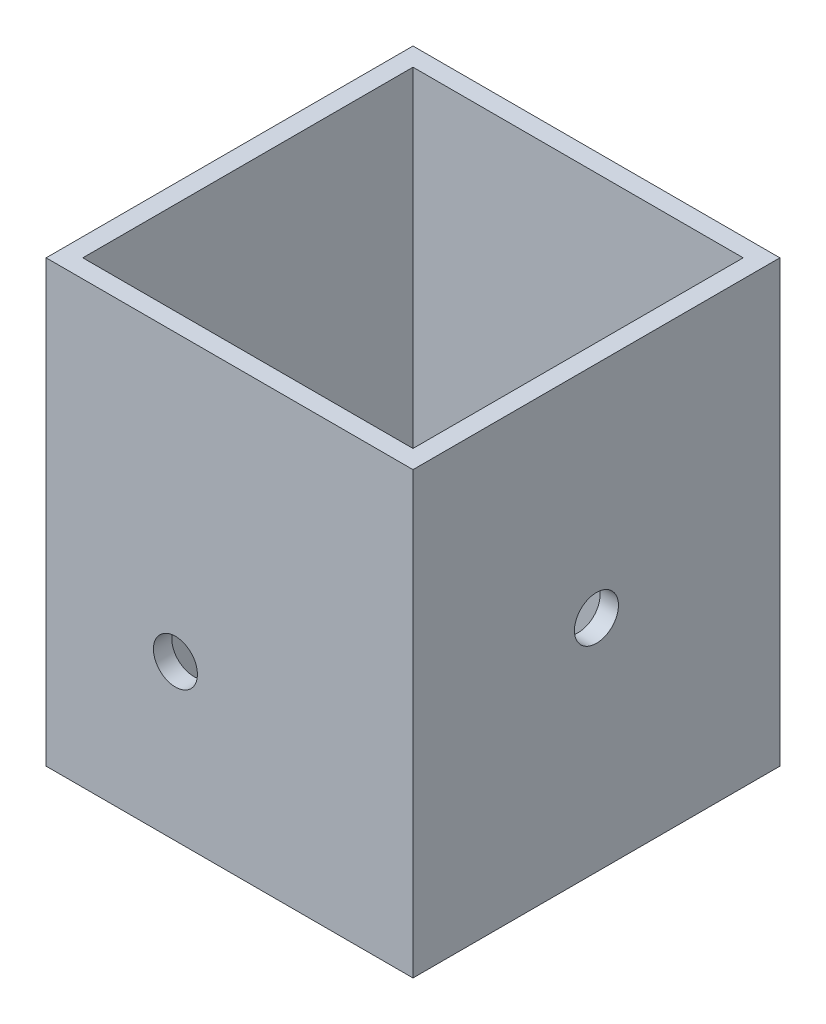
SolidWorks part; units mm, degrees
ref_plane "Front Plane" through (0, 0, 0) normal (0, 0, 1) x (1, 0, 0)
ref_plane "Top Plane" through (0, 0, 0) normal (0, 1, 0) x (1, 0, 0)
ref_plane "Right Plane" through (0, 0, 0) normal (1, 0, 0) x (0, 0, -1)
sketch "Sketch1" plane through (0, 0, 0) normal (0, 1, 0) x (1, 0, 0)
  line L1 (-12.5, 12.5) -> (12.5, 12.5)
  line L2 (-12.5, 12.5) -> (-12.5, -12.5)
  line L3 (-12.5, -12.5) -> (12.5, -12.5)
  line L4 (12.5, 12.5) -> (12.5, -12.5)
  line L5 (-12.5, 12.5) -> (12.5, -12.5) construction
  line L6 (-12.5, -12.5) -> (12.5, 12.5) construction
  line L7 (11.2504, 11.2504) -> (-11.2504, 11.2504)
  line L8 (11.2504, 11.2504) -> (11.2504, -11.2504)
  line L9 (11.2504, -11.2504) -> (-11.2504, -11.2504)
  line L10 (-11.2504, 11.2504) -> (-11.2504, -11.2504)
  line L11 (11.2504, 11.2504) -> (-11.2504, -11.2504) construction
  line L12 (11.2504, -11.2504) -> (-11.2504, 11.2504) construction
  point P0 (0, 0)
  point P6 (0, 0)
extrude "Boss-Extrude1" add sketch "Sketch1" along normal blind 30
sketch "Sketch2" plane through (0, 0, -12.5) normal (0, 0, -1) x (-1, 0, 0)
  line L0 (-5.123, 21.1475) -> (30217.9884, -36246.586) construction
  line L1 (5.123, 21.1475) -> (-30217.9884, -36246.586) construction
  circle A0 centre (3.6885, 10.5738) radius 1.5
extrude "Cut-Extrude1" cut sketch "Sketch2" against normal through all
sketch "Sketch3" plane through (12.5, 0, 0) normal (1, 0, 0) x (0, 0, -1)
  line L0 (-12.5, 30) -> (12.5, 0) construction
  line L2 (-12.5, 0) -> (12.5, 30) construction
  circle A0 centre (0, 15) radius 1.5
extrude "Cut-Extrude2" cut sketch "Sketch3" against normal through all
